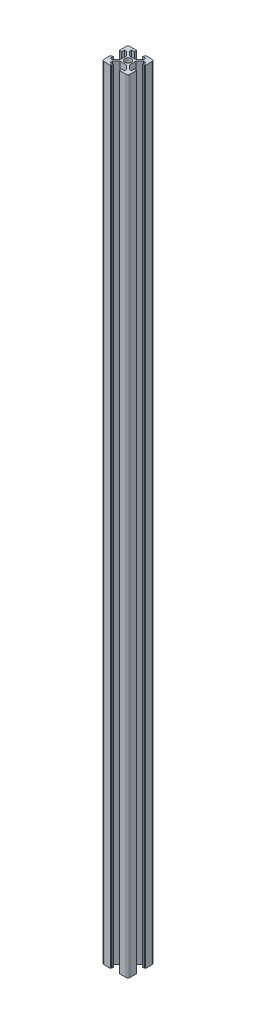
SolidWorks part; units mm, degrees
ref_plane "前视基准面" through (0, 0, 0) normal (0, 0, 1) x (1, 0, 0)
ref_plane "上视基准面" through (0, 0, 0) normal (0, 1, 0) x (1, 0, 0)
ref_plane "右视基准面" through (0, 0, 0) normal (1, 0, 0) x (0, 0, -1)
other "Configuration Table"
sketch "草图1" plane through (0, 0, 0) normal (0, 1, 0) x (1, 0, 0)
  line L0 (-5.8258, 3.4539) -> (-5.8258, 6.5539) construction
  line L1 (-5.8258, 5.9932) -> (-5.8258, 0.9145)
  line L2 (0.3135, 7.0539) -> (-4.7652, 7.0539)
  line L3 (1.3742, 0.9145) -> (1.3742, 5.9932)
  line L4 (-4.7652, -0.1461) -> (0.3135, -0.1461)
  line L5 (-12.2258, 3.4539) -> (7.7742, 3.4539) construction
  line L6 (-2.2258, 13.4539) -> (-2.2258, -6.5461) construction
  line L7 (-12.2258, 13.4539) -> (-2.2258, 3.4539) construction
  line L8 (-12.2258, 7.0539) -> (-5.8258, 7.0539) construction
  line L9 (-11.4258, 6.5539) -> (-5.3258, 6.5539) construction
  line L10 (-10.4258, 8.9539) -> (-7.7258, 8.9539) construction
  line L11 (-8.7865, 8.9539) -> (-5.8258, 5.9932) construction
  line L12 (-12.2258, 11.9539) -> (-12.2258, 7.0539)
  line L13 (-12.2258, 7.0539) -> (-11.4258, 7.0539)
  line L14 (-11.4258, 7.0539) -> (-11.4258, 6.5539)
  line L15 (-11.4258, 6.5539) -> (-10.4258, 6.5539)
  line L16 (-10.4258, 6.5539) -> (-10.4258, 8.9539)
  line L17 (-10.4258, 8.9539) -> (-8.7865, 8.9539)
  line L18 (-8.7865, 8.9539) -> (-5.8258, 5.9932)
  line L19 (-5.3258, 12.6539) -> (-5.3258, 11.6539)
  line L20 (-5.8258, 12.6539) -> (-5.3258, 12.6539)
  line L21 (-5.8258, 13.4539) -> (-5.8258, 12.6539)
  line L22 (-10.7258, 13.4539) -> (-5.8258, 13.4539)
  line L23 (-5.3258, 11.6539) -> (-7.7258, 11.6539)
  line L24 (-7.7258, 11.6539) -> (-7.7258, 10.0145)
  line L25 (-7.7258, 10.0145) -> (-4.7652, 7.0539)
  line L26 (7.7742, 13.4539) -> (-2.2258, 3.4539) construction
  line L27 (3.2742, 10.0145) -> (0.3135, 7.0539)
  line L28 (3.2742, 11.6539) -> (3.2742, 10.0145)
  line L29 (0.8742, 11.6539) -> (3.2742, 11.6539)
  line L30 (0.8742, 12.6539) -> (0.8742, 11.6539)
  line L31 (1.3742, 12.6539) -> (0.8742, 12.6539)
  line L32 (1.3742, 13.4539) -> (1.3742, 12.6539)
  line L33 (6.2742, 13.4539) -> (1.3742, 13.4539)
  line L34 (7.7742, 11.9539) -> (7.7742, 7.0539)
  line L35 (7.7742, 7.0539) -> (6.9742, 7.0539)
  line L36 (6.9742, 7.0539) -> (6.9742, 6.5539)
  line L37 (6.9742, 6.5539) -> (5.9742, 6.5539)
  line L38 (5.9742, 6.5539) -> (5.9742, 8.9539)
  line L39 (5.9742, 8.9539) -> (4.3348, 8.9539)
  line L40 (4.3348, 8.9539) -> (1.3742, 5.9932)
  line L41 (7.7742, -6.5461) -> (-2.2258, 3.4539) construction
  line L42 (4.3348, -2.0461) -> (1.3742, 0.9145)
  line L43 (5.9742, -2.0461) -> (4.3348, -2.0461)
  line L44 (5.9742, 0.3539) -> (5.9742, -2.0461)
  line L45 (6.9742, 0.3539) -> (5.9742, 0.3539)
  line L46 (6.9742, -0.1461) -> (6.9742, 0.3539)
  line L47 (7.7742, -0.1461) -> (6.9742, -0.1461)
  line L48 (7.7742, -5.0461) -> (7.7742, -0.1461)
  line L49 (6.2742, -6.5461) -> (1.3742, -6.5461)
  line L50 (1.3742, -6.5461) -> (1.3742, -5.7461)
  line L51 (1.3742, -5.7461) -> (0.8742, -5.7461)
  line L52 (0.8742, -5.7461) -> (0.8742, -4.7461)
  line L53 (0.8742, -4.7461) -> (3.2742, -4.7461)
  line L54 (3.2742, -4.7461) -> (3.2742, -3.1068)
  line L55 (3.2742, -3.1068) -> (0.3135, -0.1461)
  line L56 (-12.2258, -6.5461) -> (-2.2258, 3.4539) construction
  line L57 (-7.7258, -3.1068) -> (-4.7652, -0.1461)
  line L58 (-7.7258, -4.7461) -> (-7.7258, -3.1068)
  line L59 (-5.3258, -4.7461) -> (-7.7258, -4.7461)
  line L60 (-5.3258, -5.7461) -> (-5.3258, -4.7461)
  line L61 (-5.8258, -5.7461) -> (-5.3258, -5.7461)
  line L62 (-5.8258, -6.5461) -> (-5.8258, -5.7461)
  line L63 (-10.7258, -6.5461) -> (-5.8258, -6.5461)
  line L64 (-12.2258, -5.0461) -> (-12.2258, -0.1461)
  line L65 (-12.2258, -0.1461) -> (-11.4258, -0.1461)
  line L66 (-11.4258, -0.1461) -> (-11.4258, 0.3539)
  line L67 (-11.4258, 0.3539) -> (-10.4258, 0.3539)
  line L68 (-10.4258, 0.3539) -> (-10.4258, -2.0461)
  line L69 (-10.4258, -2.0461) -> (-8.7865, -2.0461)
  line L70 (-8.7865, -2.0461) -> (-5.8258, 0.9145)
  arc A0 (-12.2258, 11.9539) -> (-10.7258, 13.4539) centre (-10.7258, 11.9539) cw
  circle A1 centre (-2.2258, 3.4539) radius 2.5
  arc A2 (6.2742, 13.4539) -> (7.7742, 11.9539) centre (6.2742, 11.9539) cw
  arc A3 (7.7742, -5.0461) -> (6.2742, -6.5461) centre (6.2742, -5.0461) cw
  arc A4 (-10.7258, -6.5461) -> (-12.2258, -5.0461) centre (-10.7258, -5.0461) cw
  point P13 (-2.2258, 3.4539)
  point P84 (-2.2258, 3.4539)
  dimension "D8" = 1.5
  dimension "D9" = 5
  dimension "D1" = 20
  dimension "D2" = 6.2
  dimension "D3" = 7.2
  dimension "D4" = 11
  dimension "D5" = 1.5
  dimension "D6" = 0.8
  dimension "D7" = 1.8
  dimension "D10" = 7.2
extrude "凸台-拉伸1" add sketch "草图1" along normal blind 600
sketch "草图2" plane through (0, 0, -7.0539) normal (0, 0, -1) x (-1, 0, 0)
  line L0 (2.2258, 600) -> (2.2258, -49400) construction
  line L1 (-0.3135, 600) -> (4.7652, 600) construction
  line L2 (-0.3135, 0) -> (4.7652, 0) construction
  line L3 (-117.7742, 140) -> (-117.7742, 50140) construction
  line L4 (-317.7742, 140) -> (82.2258, 140) construction
  line L5 (-317.7742, 461.5) -> (82.2258, 461.5) construction
  line L9 (-6.2742, 0) -> (-1.3742, 0) construction
  line L10 (12.2258, 300) -> (-49987.7742, 300) construction
  line L11 (12.2258, 600) -> (12.2258, 0) construction
  line L12 (-246.2742, 600) -> (-246.2742, 0) construction
  circle A1 centre (2.2258, 130) radius 1.75
  circle A2 centre (2.2258, 470) radius 1.75
  point P4 (2.2258, 600)
  point P7 (2.2258, 0)
  point P12 (-117.7742, 140)
  point P15 (-117.7742, 461.5)
  point P24 (12.2258, 300)
  point P27 (-246.2742, 300)
  dimension "D1" = 3.5
  dimension "D2" = 130
extrude "切除-拉伸1" cut sketch "草图2" against normal blind 21
